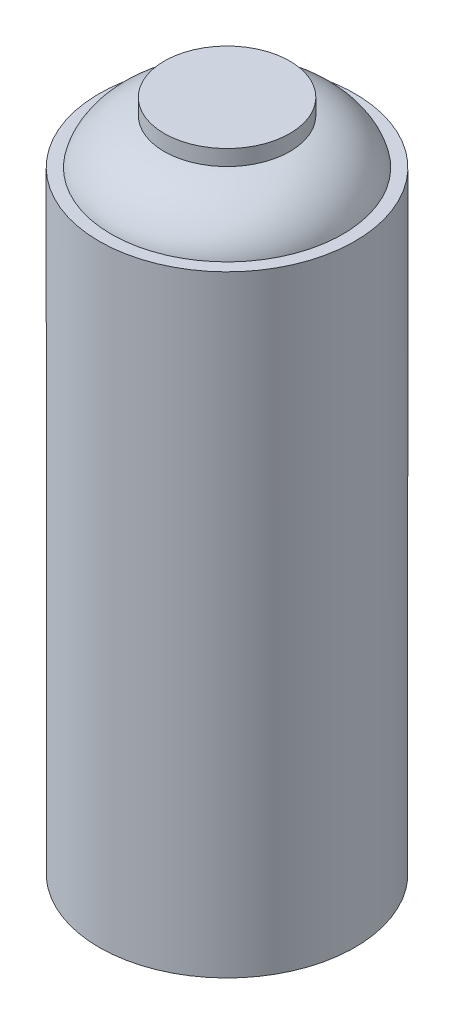
SolidWorks part; units mm, degrees
ref_plane "Front Plane" through (0, 0, 0) normal (0, 0, 1) x (1, 0, 0)
ref_plane "Top Plane" through (0, 0, 0) normal (0, 1, 0) x (1, 0, 0)
ref_plane "Right Plane" through (0, 0, 0) normal (1, 0, 0) x (0, 0, -1)
sketch "Sketch1" plane through (0, 0, 0) normal (0, 0, 1) x (1, 0, 0)
  line L0 (0, 102.2904) -> (0, -64.2269)
  line L1 (33.04, -71.4096) -> (33.04, 86.5904)
  line L2 (33.04, 86.5904) -> (29.9, 86.5904)
  line L3 (16.225, 98.2504) -> (16.225, 102.2904)
  line L4 (16.225, 102.2904) -> (0, 102.2904)
  arc A0 (0, -64.2269) -> (33.04, -71.4096) centre (0, -143.8096) cw
  spline S0 degree 3 poles (29.9, 86.5904) (28.948, 91.0519) (23.9312, 96.6173) (16.225, 98.2504) knots 0 0 0 0 1 1 1 1
  point P8 (26.7242, 92.3429)
  point P12 (0, 0)
  point P13 (4.3146, 102.109)
  point P14 (0, 102.109)
  point P15 (0.2774, 102.109)
  dimension "D7" = 79.5827
  dimension "D1" = 33.04
  dimension "D2" = 158
  dimension "D3" = 15.7
  dimension "D4" = 3.14
  dimension "D5" = 16.225
  dimension "D6" = 4.04
  dimension "D8" = 26.7242
  dimension "D9" = 86.5904
  dimension "D10" = 92.3429
revolve "Revolve1" add sketch "Sketch1" angle 360 about L0
